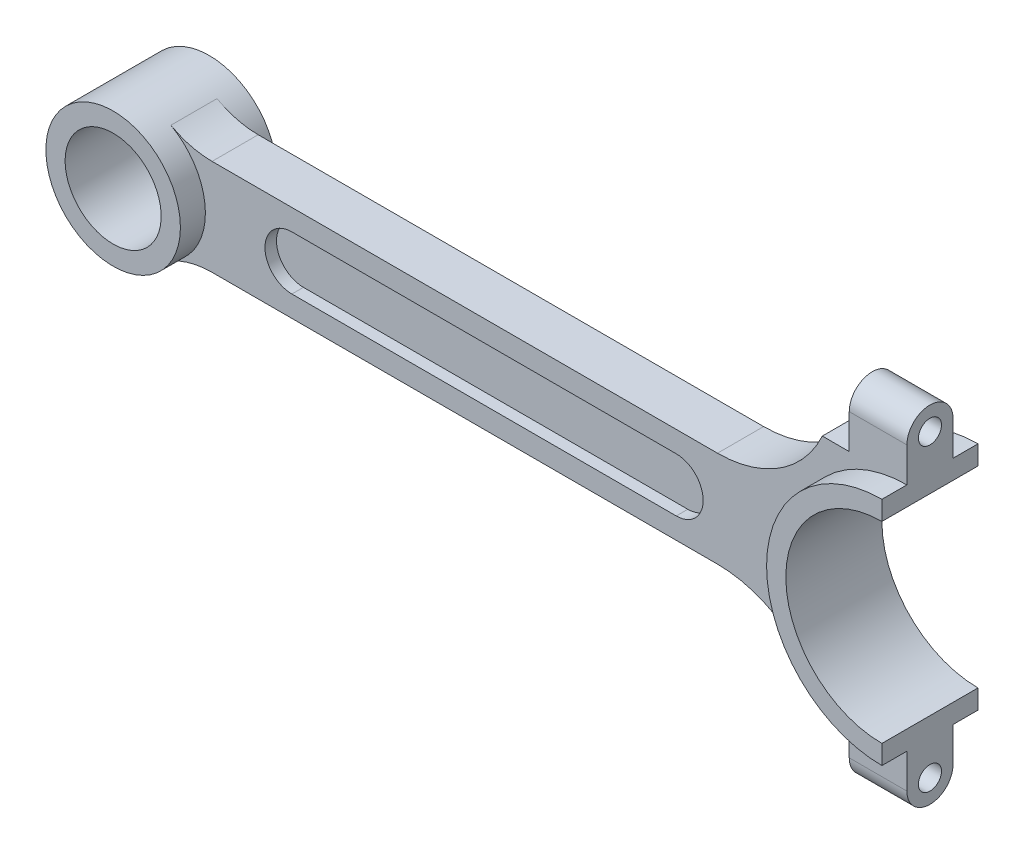
SolidWorks part; units mm, degrees
ref_plane "Front Plane" through (0, 0, 0) normal (0, 0, 1) x (1, 0, 0)
ref_plane "Top Plane" through (0, 0, 0) normal (0, 1, 0) x (1, 0, 0)
ref_plane "Right Plane" through (0, 0, 0) normal (1, 0, 0) x (0, 0, -1)
sketch "Sketch1" plane through (0, 0, 0) normal (0, 0, 1) x (1, 0, 0)
  line L0 (0, 0) -> (5080, 0) construction
  line L1 (5080, 762) -> (5080, 635)
  line L2 (5080, -635) -> (5080, -762)
  circle A0 centre (0, 0) radius 317.5
  circle A1 centre (0, 0) radius 444.5
  arc A2 (5080, 635) -> (5080, -635) centre (5080, 0) ccw
  arc A3 (5080, 762) -> (5080, -762) centre (5080, 0) ccw
  dimension "D1" = 889
  dimension "D2" = 635
  dimension "D3" = 1524
  dimension "D4" = 1270
  dimension "D5" = 5080
extrude "Boss-Extrude1" add sketch "Sketch1" along normal mid plane 635
sketch "Sketch2" plane through (0, 0, 0) normal (0, 0, 1) x (1, 0, 0)
  line L0 (444.5, 0) -> (4318, 0) construction
  line L1 (311.0852, 317.5) -> (4318, 317.5)
  line L2 (5080, 762) -> (4521.2, 762)
  line L3 (4521.2, 762) -> (4318, 317.5)
  line L4 (444.5, 317.5) -> (4318, 317.5) construction
  line L5 (4521.2, -762) -> (4318, -317.5)
  line L6 (5080, -762) -> (4521.2, -762)
  line L7 (311.0852, -317.5) -> (4318, -317.5)
  circle A0 centre (0, 0) radius 444.5 construction
  arc A1 (5080, 762) -> (5080, -762) centre (5080, 0) ccw construction
  arc A2 (311.0852, -317.5) -> (311.0852, 317.5) centre (0, 0) ccw
  arc A3 (5080, 762) -> (5080, -762) centre (5080, 0) ccw
  point P12 (311.0852, 317.5)
  dimension "D2" = 558.8
  dimension "D1" = 317.5
extrude "Boss-Extrude2" add sketch "Sketch2" along normal mid plane 304.8
fillet "Fillet1" radius 558.8 2 edges at (311.0852, -317.5, 0) (311.0852, 317.5, 0)
fillet "Fillet2" radius 762 2 edges at (4318, -317.5, 0) (4318, 317.5, 0)
sketch "Sketch4" plane through (5080, 0, 0) normal (1, 0, 0) x (0, 0, -1)
  line L0 (0, 1143) -> (-561.1572, 1143) construction
  line L1 (-317.5, 762) -> (-152.4, 762) construction
  line L2 (-152.4, 990.6) -> (-152.4, 762)
  line L3 (152.4, 990.6) -> (152.4, 762)
  arc A0 (152.4, 990.6) -> (-152.4, 990.6) centre (0, 990.6) ccw
  circle A1 centre (0, 990.6) radius 76.2
  line M6 (152.4, 762) -> (-152.4, 762)
  dimension "D1" = 152.4
  dimension "D2" = 304.8
  dimension "D3" = 381
extrude "Boss-Extrude3" add sketch "Sketch4" against normal blind 381 contours L3 A0 L2 A1 M6 region at (5080, 1138.1208, 0)
mirror "Mirror1" about plane through (0, 0, 0) normal (0, 1, 0) of "Boss-Extrude3"
sketch "Sketch5" plane through (0, 0, 152.4) normal (0, 0, 1) x (1, 0, 0)
  line L0 (0, 0) -> (4318, 0) construction
  line L1 (3556, 0) -> (1016, 0) construction
  line L2 (3556, -177.8) -> (1016, -177.8)
  line L3 (3556, 177.8) -> (1016, 177.8)
  arc A0 (5080, 762) -> (5080, -762) centre (5080, 0) ccw construction
  arc A1 (3556, -177.8) -> (3556, 177.8) centre (3556, 0) ccw
  arc A2 (1016, 177.8) -> (1016, -177.8) centre (1016, 0) ccw
  point P8 (2286, 0)
  dimension "D1" = 177.8
  dimension "D2" = 2540
  dimension "D3" = 1016
extrude "Cut-Extrude1" cut sketch "Sketch5" against normal blind 76.2
mirror "Mirror2" about plane through (0, 0, 0) normal (0, 0, 1) of "Cut-Extrude1"
